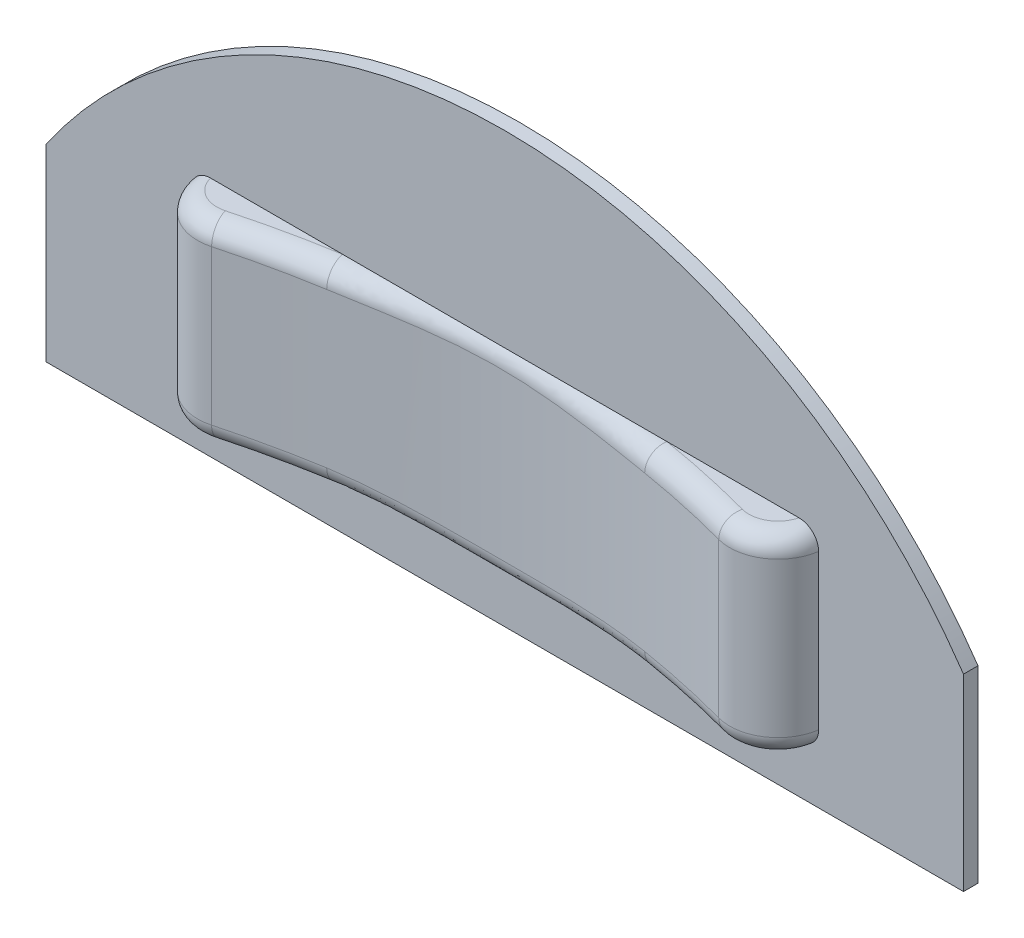
SolidWorks part; units mm, degrees
ref_plane "Front Plane" through (0, 0, 0) normal (0, 0, 1) x (1, 0, 0)
ref_plane "Top Plane" through (0, 0, 0) normal (0, 1, 0) x (1, 0, 0)
ref_plane "Right Plane" through (0, 0, 0) normal (1, 0, 0) x (0, 0, -1)
sketch "Sketch1" plane through (0, 0, 0) normal (0, 0, 1) x (1, 0, 0)
  line L0 (190, 0) -> (190, -39)
  line L1 (0, 0) -> (0, -39)
  line L2 (0, -39) -> (190, -39)
  arc A0 (0, 0) -> (190, 0) centre (95, -65.25) cw
  point P3 (95, 50)
  dimension "D1" = 50
  dimension "D2" = 39
  dimension "D3" = 39
  dimension "D4" = 190
extrude "Boss-Extrude1" add sketch "Sketch1" along normal blind 3 contours L2 L0 A0 L1
sketch "Sketch2" plane through (0, 0, 3) normal (0, 0, 1) x (1, 0, 0)
  line L0 (0, -39) -> (190, -39) construction
  line L1 (30, 11) -> (160, 11)
  line L2 (30, 11) -> (30, -29)
  line L3 (30, -29) -> (160, -29)
  line L4 (160, 11) -> (160, -29)
  line L5 (190, 0) -> (190, -39) construction
  line L6 (0, 0) -> (0, -39) construction
  dimension "D1" = 10
  dimension "D2" = 30
  dimension "D3" = 30
  dimension "D4" = 40
extrude "Boss-Extrude2" add sketch "Sketch2" along normal blind 12
sketch "Sketch3" plane through (0, 11, 0) normal (0, 1, 0) x (1, 0, 0)
  line L0 (160, -15) -> (160, -3) construction
  line L1 (160, -15) -> (30, -15) construction
  line L2 (30, -15) -> (160, -15)
  arc A0 (30, -15) -> (160, -15) centre (95, -205.9744) cw
extrude "Cut-Extrude1" cut sketch "Sketch3" against normal up to next
fillet "Fillet1" radius 10 2 edges at (160, -9, 15) (30, -9, 15)
fillet "Fillet2" radius 4 6 edges at (155.591, -29, 9.9008) (95, -29, 4.2414) (34.409, -29, 9.9008) (155.591, 11, 9.9008) (95, 11, 4.2414) (34.409, 11, 9.9008)
